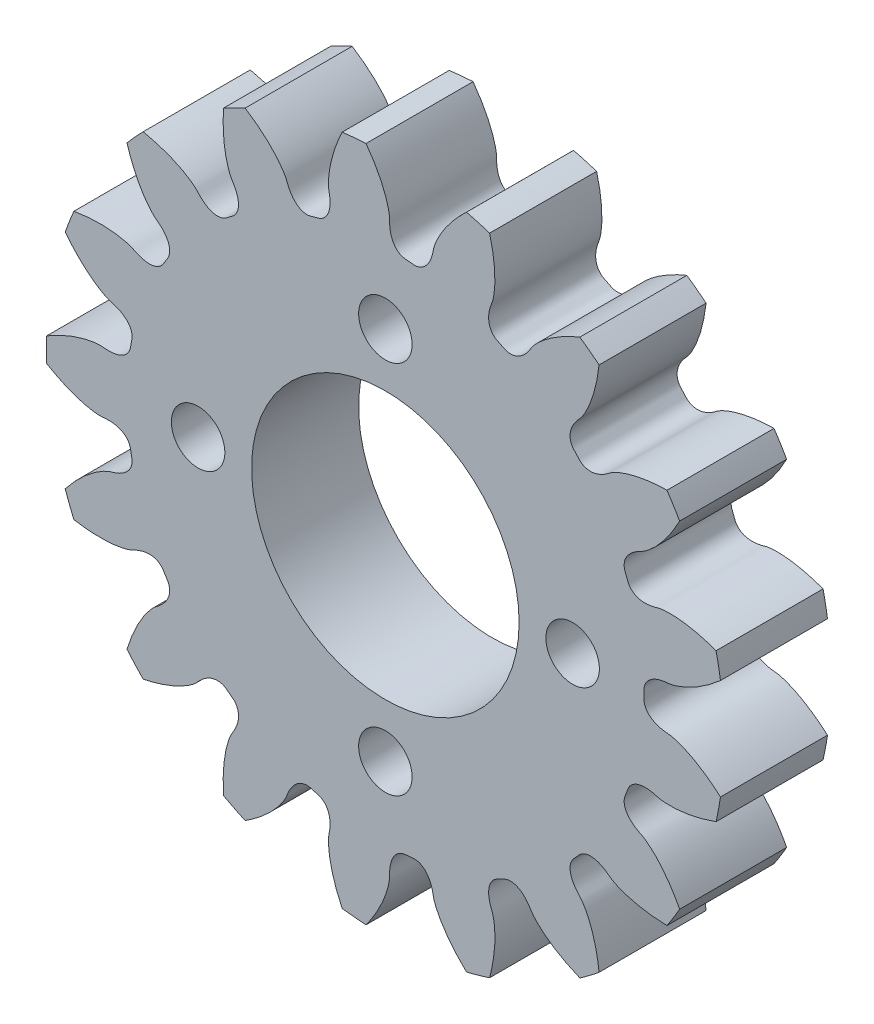
SolidWorks part; units mm, degrees
material "POM 乙缩醛共聚物"
ref_plane "前视基准面" through (0, 0, 0) normal (0, 0, 1) x (1, 0, 0)
ref_plane "上视基准面" through (0, 0, 0) normal (0, 1, 0) x (1, 0, 0)
ref_plane "右视基准面" through (0, 0, 0) normal (1, 0, 0) x (0, 0, -1)
ref_axis "基准轴1" through (0, 0, 55) along (0, 0, -1)
sketch "旋转草图小直齿轮" plane through (0, 0, 0) normal (1, 0, 0) x (0, 0, -1)
  line L0 (0, 0) -> (1, 0) construction
  line L1 (-3, 0) -> (-3, 19)
  line L2 (-3, 19) -> (3, 19)
  line L3 (3, 19) -> (3, 0)
  line L4 (3, 0) -> (-3, 0)
revolve "小直齿轮" add sketch "旋转草图小直齿轮" angle 360 about L0
sketch "齿草图小直齿轮" plane through (0, 0, 0) normal (0, 0, 1) x (1, 0, 0)
  arc A0 (18.8777, 2.9059) -> (18.8777, -2.9059) centre (0, 0) cw
  spline S0 degree 3 poles (18.8777, -2.9059) (18.7162, -2.7605) (18.4737, -2.5555) (18.1462, -2.3058) (17.9156, -2.1416) (17.694, -1.9946) (17.4824, -1.8638) (17.2814, -1.7487) (17.092, -1.6481) (16.9148, -1.5614) (16.7504, -1.4876) (16.5997, -1.4257) (16.463, -1.3747) (16.3411, -1.3337) (16.2343, -1.3016) (16.143, -1.2774) (16.0678, -1.2601) (16.0089, -1.2485) (15.9082, -1.2318) (15.8073, -1.2291) (15.7037, -1.216) (15.6495, -1.2083) (15.5963, -1.1996) (15.544, -1.19) (15.4927, -1.1794) (15.4423, -1.1677) (15.3928, -1.1551) (15.3442, -1.1414) (15.2965, -1.1266) (15.2496, -1.1108) (15.2035, -1.0937) (15.1582, -1.0755) (15.1136, -1.056) (15.0698, -1.0351) (15.0267, -1.0127) (14.9843, -0.9888) (14.9426, -0.9632) (14.9016, -0.9357) (14.8613, -0.9062) (14.8218, -0.8744) (14.7832, -0.8402) (14.7455, -0.8034) (14.709, -0.7636) (14.674, -0.7206) (14.6407, -0.6743) (14.6095, -0.6245) (14.581, -0.5711) (14.5558, -0.5142) (14.5343, -0.4538) (14.5174, -0.3904) (14.5054, -0.3246) (14.4997, -0.2626) (14.4972, -0.1542) (14.5022, 0) (14.4972, 0.1542) (14.4997, 0.2626) (14.5054, 0.3246) (14.5174, 0.3904) (14.5343, 0.4538) (14.5558, 0.5142) (14.581, 0.5711) (14.6095, 0.6245) (14.6407, 0.6743) (14.674, 0.7206) (14.709, 0.7636) (14.7455, 0.8034) (14.7832, 0.8402) (14.8218, 0.8744) (14.8613, 0.9062) (14.9016, 0.9357) (14.9426, 0.9632) (14.9843, 0.9888) (15.0267, 1.0127) (15.0698, 1.0351) (15.1136, 1.056) (15.1582, 1.0755) (15.2035, 1.0937) (15.2496, 1.1108) (15.2965, 1.1266) (15.3442, 1.1414) (15.3928, 1.1551) (15.4423, 1.1677) (15.4927, 1.1794) (15.544, 1.19) (15.5963, 1.1996) (15.6495, 1.2083) (15.7037, 1.216) (15.8073, 1.2291) (15.9082, 1.2318) (16.0089, 1.2485) (16.0678, 1.2601) (16.143, 1.2774) (16.2343, 1.3016) (16.3411, 1.3337) (16.463, 1.3747) (16.5997, 1.4257) (16.7504, 1.4876) (16.9148, 1.5614) (17.092, 1.6481) (17.2814, 1.7487) (17.4824, 1.8638) (17.694, 1.9946) (17.9156, 2.1416) (18.1462, 2.3058) (18.4737, 2.5555) (18.7162, 2.7605) (18.8777, 2.9059) knots 0 0 0 0 0.058344 0.085213 0.110547 0.134345 0.156608 0.177336 0.196528 0.214185 0.230306 0.244893 0.257943 0.269459 0.279439 0.287883 0.294792 0.300166 0.304005 0.32219 0.327162 0.332059 0.336883 0.341638 0.346326 0.350953 0.355523 0.36004 0.36451 0.36894 0.373335 0.377703 0.382053 0.386393 0.390734 0.395086 0.399462 0.403875 0.408338 0.412867 0.417479 0.422188 0.427012 0.431965 0.437063 0.442315 0.447728 0.453304 0.459035 0.464908 0.470898 0.476975 0.481621 0.5 0.518379 0.523025 0.529102 0.535092 0.540965 0.546696 0.552272 0.557685 0.562937 0.568035 0.572988 0.577812 0.582521 0.587133 0.591662 0.596125 0.600538 0.604914 0.609266 0.613607 0.617947 0.622297 0.626665 0.63106 0.63549 0.63996 0.644477 0.649047 0.653674 0.658362 0.663117 0.667941 0.672838 0.67781 0.695995 0.699834 0.705208 0.712117 0.720561 0.730541 0.742057 0.755107 0.769694 0.785815 0.803472 0.822664 0.843392 0.865655 0.889453 0.914787 0.941656 1 1 1 1
extrude "齿拉伸切除小直齿轮" cut sketch "齿草图小直齿轮" against normal blind 3 and the other way blind 3
pattern_circular "齿形小直齿轮" count 17 every 21.176 about axis through (0, 0, 55) along (0, 0, -1) of "齿拉伸切除小直齿轮"
sketch "孔旋转草图" plane through (0, 0, 0) normal (1, 0, 0) x (0, 0, -1)
  line L0 (0, 0) -> (1, 0) construction
  line L1 (-3, 0) -> (3, 0)
  line L2 (3, 0) -> (3, 7.5)
  line L3 (3, 7.5) -> (-3, 7.5)
  line L4 (-3, 7.5) -> (-3, 0)
  dimension "D1" = 6
  dimension "TaperSide1" = 7.5
  dimension "D2" = 3
revolve "孔旋转切除" cut sketch "孔旋转草图" angle 360 about L0
sketch "辅助草图小直齿轮" plane through (0, 0, 0) normal (0, 0, 1) x (1, 0, 0)
  circle A0 centre (0, 0) radius 17 construction
  circle A1 centre (0, 0) radius 15.9748 construction
  circle A2 centre (0, 0) radius 15.9784 construction
  circle A3 centre (0, 0) radius 19 construction
  circle A4 centre (0, 0) radius 14.5 construction
  dimension "PitchDiameter" = 34
  dimension "BaseDiameter" = 31.9495
  dimension "FormDiameter" = 31.9568
  dimension "MajorDiameter" = 38
  dimension "MinorDiameter" = 29
sketch "草图1" plane through (0, 0, -3) normal (0, 0, -1) x (-1, 0, 0)
  line L0 (0, 21.5315) -> (0, -5.4855) construction
  line L1 (-22.3981, 0) -> (23.4659, 0) construction
  circle A0 centre (0, 10.5) radius 1.5
  circle A1 centre (10.5, 0) radius 1.5
  circle A2 centre (0, -10.5) radius 1.5
  circle A3 centre (-10.5, 0) radius 1.5
  point P15 (0, 0)
  dimension "D1" = 4
  dimension "D3" = 3
  dimension "D2" = 21
extrude "切除-拉伸1" cut sketch "草图1" against normal through all
